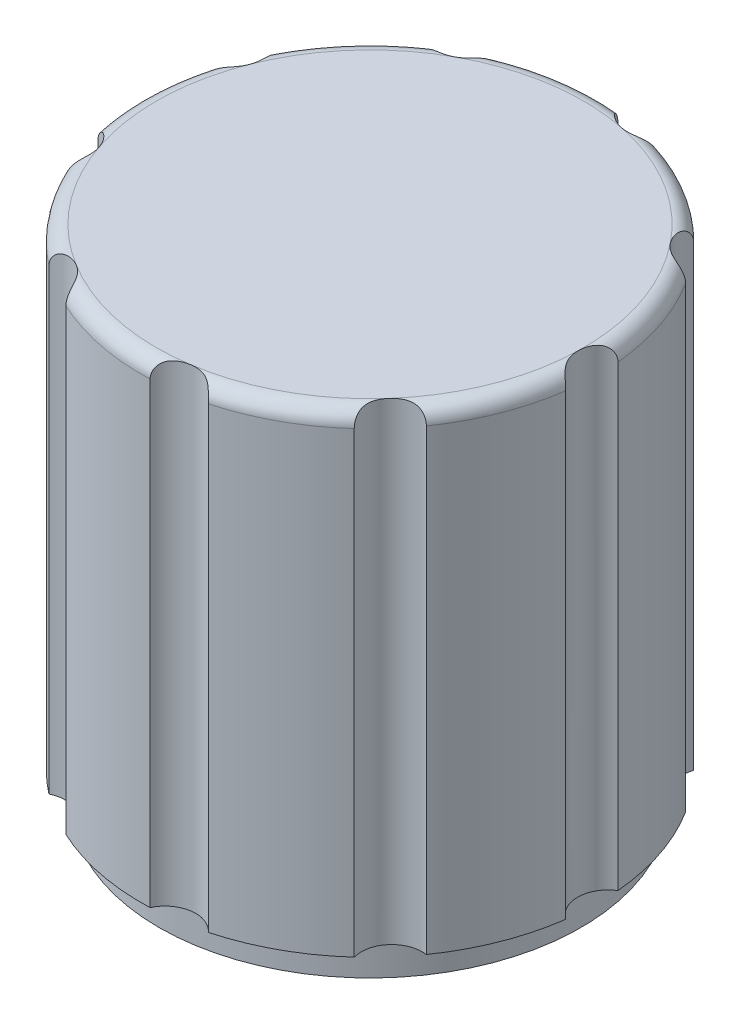
SolidWorks part; units mm, degrees
material "Custom Plastic"
ref_plane "Front Plane" through (0, 0, 0) normal (0, 0, 1) x (1, 0, 0)
ref_plane "Top Plane" through (0, 0, 0) normal (0, 1, 0) x (1, 0, 0)
ref_plane "Right Plane" through (0, 0, 0) normal (1, 0, 0) x (0, 0, -1)
sketch "Sketch1" plane through (0, 0, 0) normal (0, 1, 0) x (1, 0, 0)
  circle A0 centre (0, 0) radius 7.5
  dimension "D1" = 15
extrude "Boss-Extrude1" add sketch "Sketch1" along normal blind 16.5
fillet "Fillet1" radius 0.5 1 edges at (0, 16.5, 7.5)
sketch "Sketch2" plane through (0, 0, 0) normal (0, -1, 0) x (1, 0, 0)
  circle A0 centre (0, 0) radius 2.7504
extrude "Cut-Extrude1" cut sketch "Sketch2" against normal blind 5 contours A0
sketch "Sketch3" plane through (0, 0, 0) normal (0, -1, 0) x (1, 0, 0)
  circle A0 centre (0, 0) radius 6.915
  circle A1 centre (0, 0) radius 7.5
extrude "Cut-Extrude2" cut sketch "Sketch3" against normal blind 1
sketch "Sketch4" plane through (0, 16.5, 0) normal (0, 1, 0) x (1, 0, 0)
  circle A0 centre (1.1989, -7.9097) radius 1
  circle A1 centre (0, 0) radius 7 construction
  circle A2 centre (-4.1658, -6.8298) radius 1
  circle A3 centre (-7.5813, -2.5542) radius 1
  circle A4 centre (-7.4494, 2.9165) radius 1
  circle A5 centre (-3.8319, 7.0226) radius 1
  circle A6 centre (1.5786, 7.8427) radius 1
  circle A7 centre (6.2505, 4.9931) radius 1
  circle A8 centre (7.9977, -0.1928) radius 1
  circle A9 centre (6.0027, -5.2885) radius 1
  dimension "D1" = 2
  dimension "D2" = 14
  dimension "D3" = 9
extrude "Cut-Extrude3" cut sketch "Sketch4" against normal through all
